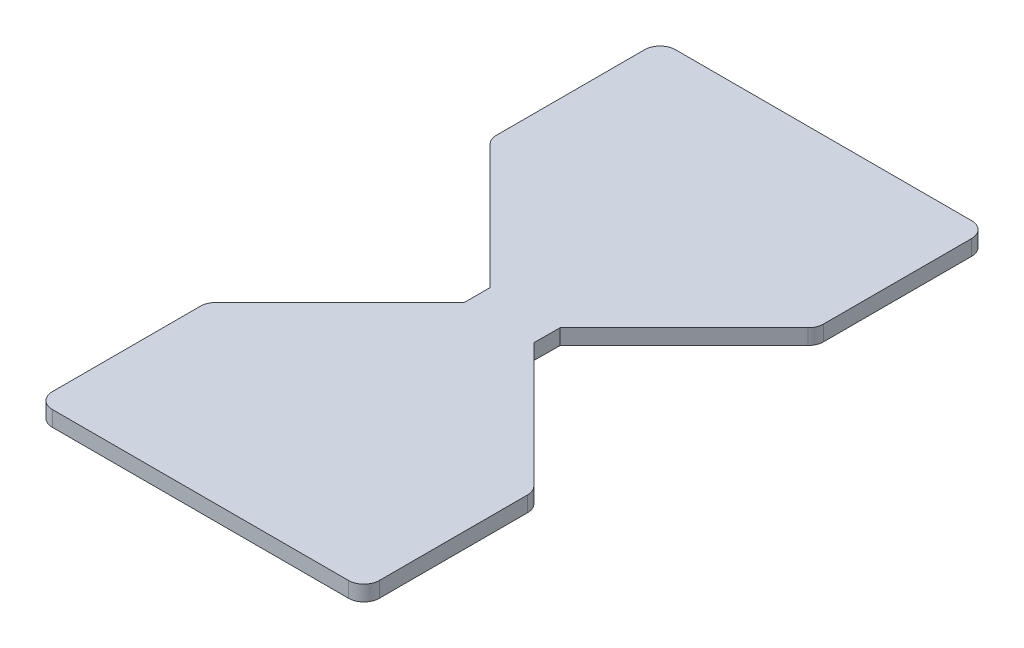
SolidWorks part; units mm, degrees
ref_plane "前视基准面" through (0, 0, 0) normal (0, 0, 1) x (1, 0, 0)
ref_plane "上视基准面" through (0, 0, 0) normal (0, 1, 0) x (1, 0, 0)
ref_plane "右视基准面" through (0, 0, 0) normal (1, 0, 0) x (0, 0, -1)
other "Configuration Table"
sketch "草图1" plane through (0, 0, 0) normal (0, 1, 0) x (1, 0, 0)
  line L18 (0, -2.4) -> (46, -2.4)
  line L20 (-2.4, 23) -> (-2.4, 0)
  line L22 (48.4, 23) -> (48.4, 0)
  line L25 (28.4083, 43.9858) -> (47.6971, 24.6971)
  line L28 (17.5998, 43.9939) -> (-1.6971, 24.6971)
  line L32 (-1.6971, 67.3026) -> (17.5998, 48.0057)
  line L33 (46, 68.9996) -> (46.8485, 68.1511)
  line L34 (47.6971, 67.3026) -> (28.4417, 48.0472)
  line L37 (48.4, 68.9996) -> (48.4, 91.9996)
  line L39 (46, 91.9996) -> (46, 93.1996)
  line L40 (46, 94.3996) -> (0, 94.3996)
  line L44 (-2.4, 91.9996) -> (-2.4, 68.9996)
  line L66 (17.5998, 43.9939) -> (17.5998, 48.0057)
  line L68 (28.4417, 48.0472) -> (28.4083, 43.9858)
  arc A0 (-2.4, 0) -> (0, -2.4) centre (0, 0) ccw
  arc A1 (46, -2.4) -> (48.4, 0) centre (46, 0) ccw
  arc A2 (47.6971, 24.6971) -> (48.4, 23) centre (46, 23) cw
  arc A3 (-2.4, 23) -> (-1.6971, 24.6971) centre (0, 23) cw
  arc A4 (-2.4, 68.9996) -> (-1.6971, 67.3026) centre (0, 68.9996) ccw
  arc A5 (48.4, 68.9996) -> (47.6971, 67.3026) centre (46, 68.9996) cw
  arc A6 (46, 94.3996) -> (48.4, 91.9996) centre (46, 91.9996) cw
  arc A7 (0, 94.3996) -> (-2.4, 91.9996) centre (0, 91.9996) ccw
  arc A8 (0, 93.1996) -> (-1.2, 91.9996) centre (0, 91.9996) ccw
  point P3 (0, 0)
  point P5 (0, 0)
  point P9 (0, 0)
  point P12 (0, 0)
  point P39 (-1.2, 91.9996)
  point P40 (0, 93.1996)
  point P41 (46, 92.5996)
  point P42 (47.2, 91.9996)
  point P43 (47.2, 68.9996)
  point P44 (-1.8, 68.9996)
  point P45 (-1.2728, 67.7268)
  point P46 (46.8485, 68.1511)
  point P49 (46.8485, 23.8485)
  point P50 (47.2, 23)
  point P51 (-1.2, 23)
  point P52 (-0.8485, 23.8485)
extrude "凸台-拉伸1" add sketch "草图1" against normal blind 2.4 contours L40 A7 L44 A4 L32 L66 L28 A3 L20 A0 L18 A1 L22 A2 L25 L68 L34 A5 L37 A6 region at (23.0001, 0, -45.9998)
